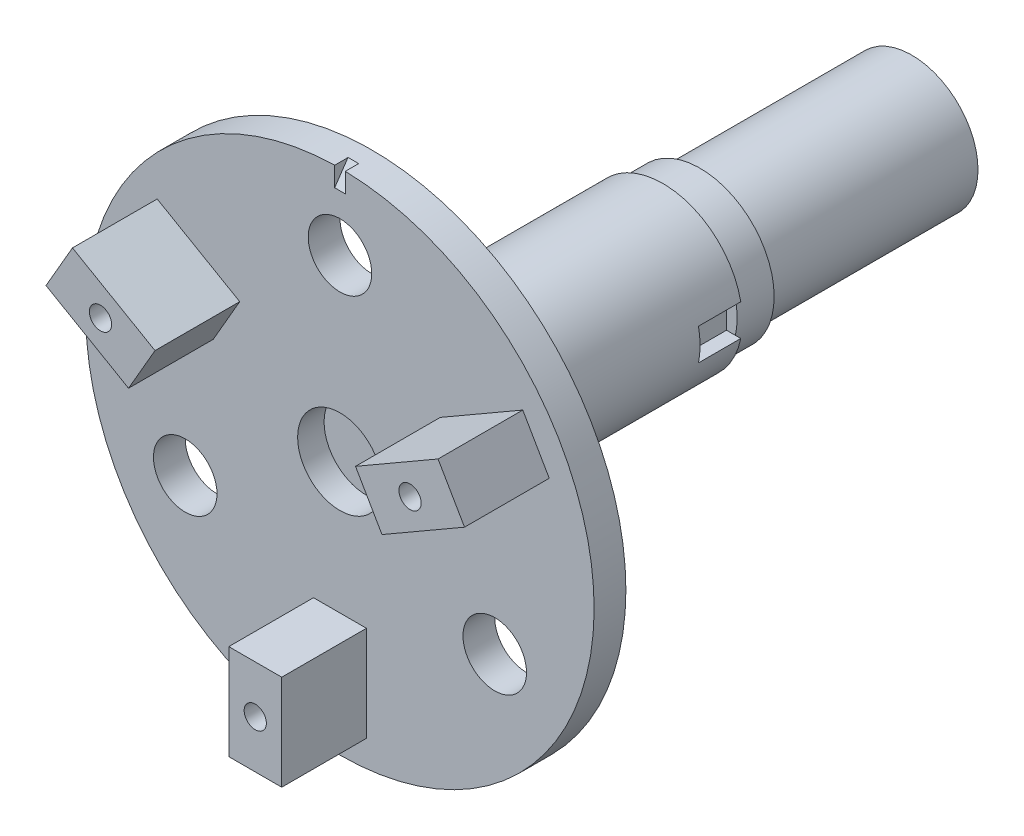
SolidWorks part; units mm, degrees
material "1.7225 (42CrMo4)"
ref_plane "Front Plane" through (0, 0, 0) normal (0, 0, 1) x (1, 0, 0)
ref_plane "Top Plane" through (0, 0, 0) normal (0, 1, 0) x (1, 0, 0)
ref_plane "Right Plane" through (0, 0, 0) normal (1, 0, 0) x (0, 0, -1)
sketch "Sketch1" plane through (0, 0, 0) normal (0, 0, 1) x (1, 0, 0)
  circle A0 centre (0, 0) radius 48
  circle A1 centre (0, 0) radius 8
  dimension "D1" = 96
  dimension "D2" = 16
extrude "EX_Carrier_Front_Plate_4mm" add sketch "Sketch1" along normal mid plane 6
sketch "Sketch2" plane through (0, 0, 3) normal (0, 0, 1) x (1, 0, 0)
  line L0 (0, 0) -> (0, 33.75) construction
  circle A0 centre (0, 33.75) radius 6
  dimension "D2" = 12
  dimension "D1" = 33.75
extrude "CUT_Pin_Hole_Ø12" cut sketch "Sketch2" against normal through all both and the other way through all contours A0
pattern_circular "PAT_Pin_Holes_3x120" count 3 over 360 about axis through (0, 0, 3) along (0, 0, 1) of "CUT_Pin_Hole_Ø12"
sketch "Sketch3" plane through (0, 0, 0) normal (1, 0, 0) x (0, 0, -1)
  line L0 (-0.4769, 48) -> (-3, 44.3)
  line L1 (3, 48) -> (-3, 48) construction
  line L2 (-3, 48) -> (-3, -48) construction
  line L3 (-3, 44.3) -> (-3, 48)
  line L4 (-3, 48) -> (-0.4769, 48)
extrude "Cut-Extrude1" cut sketch "Sketch3" against normal mid plane 2
ref_axis "Axis1" through (0, 0, -3.3083) along (0, 0, 1)
sketch "Sketch4" plane through (0, 0, 0) normal (0, 0, 1) x (1, 0, 0)
  line L0 (-5, -24.75) -> (5, -24.75)
  line L1 (5, -24.75) -> (5, -42.75)
  line L2 (5, -42.75) -> (-5, -42.75)
  line L3 (-5, -42.75) -> (-5, -24.75)
extrude "Boss-Extrude1" add sketch "Sketch4" along normal blind 19
sketch "Sketch5" plane through (0, 0, 19) normal (0, 0, 1) x (1, 0, 0)
  circle A0 centre (0, -33.75) radius 2.1
extrude "Cut-Extrude3" cut sketch "Sketch5" against normal blind 12
pattern_circular "CirPattern1" count 3 over 360 about axis through (0, 0, -3.3083) along (0, 0, 1) of "Boss-Extrude1"
pattern_circular "CirPattern2" count 3 over 360 about axis through (0, 0, -3.3083) along (0, 0, 1) of "Cut-Extrude3"
sketch "Sketch6" plane through (0, 0, 0) normal (1, 0, 0) x (0, 0, -1)
  line L0 (2, 0) -> (2, 18)
  line L1 (2, 18) -> (6, 18)
  line L2 (6, 18) -> (6, 15)
  line L3 (6, 15) -> (58, 15)
  line L4 (58, 15) -> (58, 14)
  line L5 (58, 14) -> (65, 14)
  line L6 (65, 14) -> (65, 12.5)
  line L7 (65, 12.5) -> (105, 12.5)
  line L8 (105, 12.5) -> (105, 0)
  line L9 (105, 0) -> (2, 0)
  line L10 (-4, 0) -> (0, 0) construction
revolve "Revolve1" add sketch "Sketch6" angle 360 about L10
sketch "Sketch7" plane through (0, 0, 0) normal (0, 1, 0) x (1, 0, 0)
  line L1 (12, 50) -> (16.5, 50)
  line L2 (12, 50) -> (12, 58)
  line L3 (12, 58) -> (16.5, 58)
  line L4 (16.5, 50) -> (16.5, 58)
extrude "CUT_MB6_Tab_Groove_6w_M27" cut sketch "Sketch7" along normal mid plane 6
